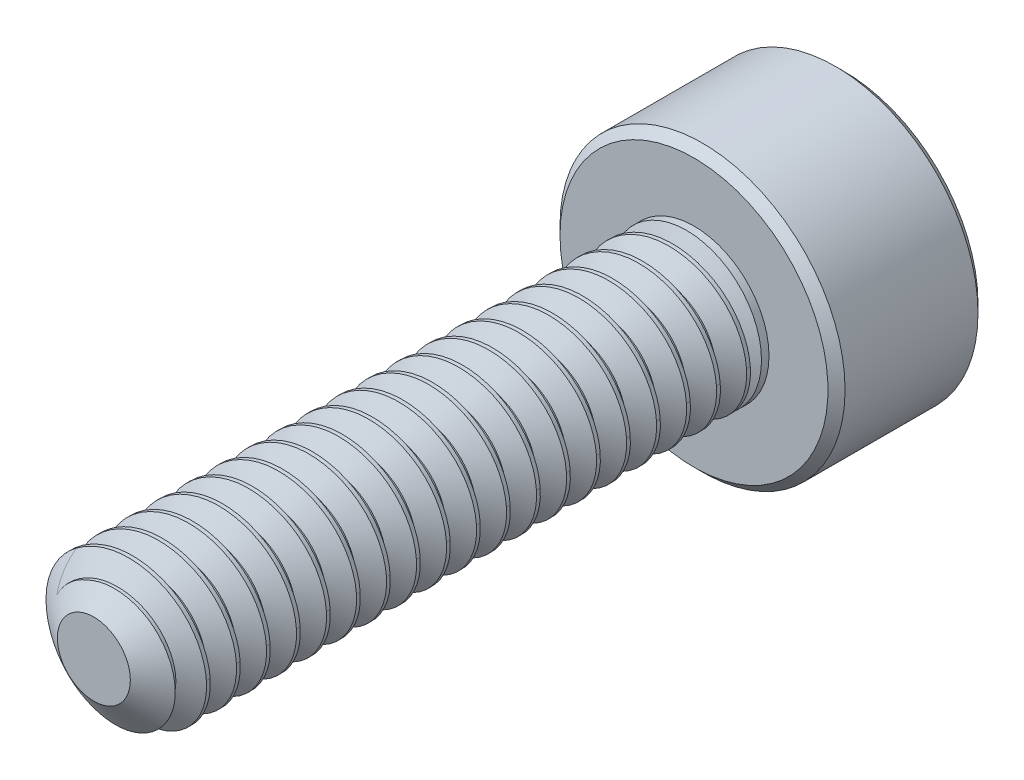
SolidWorks part; units mm, degrees
ref_plane "Front Plane" through (0, 0, 0) normal (0, 0, 1) x (1, 0, 0)
ref_plane "Top Plane" through (0, 0, 0) normal (0, 1, 0) x (1, 0, 0)
ref_plane "Right Plane" through (0, 0, 0) normal (1, 0, 0) x (0, 0, -1)
sketch "Sketch1" plane through (0, 0, 0) normal (0, 0, 1) x (1, 0, 0)
  circle A0 centre (0, 0) radius 1
  dimension "OD" = 2
extrude "Extrude1" add sketch "Sketch1" against normal blind 8
sketch "Sketch2" plane through (0, 0, 0) normal (0, 0, 1) x (1, 0, 0)
  circle A0 centre (0, 0) radius 1 construction
  circle A1 centre (0, 0) radius 1
curve "Helix/Spiral1" pitch 0.4 height 8.4 radius 1 centre (0, 0, 0) axis (0, 0, -1) start towards (0, 1, 0) parameters "pitch"=0.4
sketch "Sketch3" plane through (0, 0, 0) normal (1, 0, 0) x (0, 0, -1)
  line L0 (-0.35, 1) -> (-0.2, 0.7402)
  line L1 (-0.2, 0.7402) -> (-0.15, 0.7402)
  line L2 (-0.15, 0.7402) -> (0, 1)
  line L3 (-0.35, 1) -> (0, 1)
  line L4 (-0.175, 1) -> (-0.175, 0.7402) construction
  line L5 (-0.275, 0.8701) -> (-0.075, 0.8701) construction
  line L6 (0, 1) -> (0, -1) construction
  line L7 (0, -1) -> (8, -1) construction
  point P11 (1.8, -1)
  dimension "D1" = 0.05
  dimension "D2" = 0.2
  dimension "D3" = 60
  dimension "D4" = 1.8
sweep "Cut-Sweep1" cut profiles "Sketch3" path "Helix/Spiral1" align with end faces yes
sketch "Sketch4" plane through (0, 0, 0) normal (1, 0, 0) x (0, 0, -1)
  line L0 (0.3598, 1) -> (0, 0.4862)
  line L1 (0, 0.4862) -> (0, 1)
  line L2 (0.3598, 1) -> (0, 1)
  line L3 (-0.35, 1) -> (0, 1) construction
  line L4 (0, 0) -> (7.0209, 0) construction
  dimension "D1" = 55
  dimension "D2" = 0.254
revolve "Cut-Revolve1" cut sketch "Sketch4" angle 360 about L4
sketch "Sketch5" plane through (0, 0, 0) normal (1, 0, 0) x (0, 0, -1)
  line L0 (8, -0.7473) -> (8, 0.7135) construction
  line L1 (8, 1) -> (0.1203, 1)
  line L2 (8, 1) -> (8, 0)
  line L3 (8, 0) -> (0.0001, 0)
  line L4 (0.0001, 0.6698) -> (0.0001, 0)
  line L5 (0.1203, 1) -> (0.0001, 0.6698)
  line L6 (0, 0) -> (9.9695, 0) construction
  point P3 (0.0001, 1)
  point P10 (0.0001, 1)
  dimension "D1" = 0.3302
  dimension "Thread min" = 0.0001
  dimension "D3" = 20
revolve "partially thread" [suppressed] add sketch "Sketch5" angle 360 about L6
sketch "Sketch6" plane through (0, 0, -8) normal (0, 0, -1) x (-1, 0, 0)
  circle A0 centre (0, 0) radius 1.9
  dimension "head dia" = 3.8
extrude "Extrude2" add sketch "Sketch6" along normal blind 2
sketch "Sketch7" plane through (0, 0, -10) normal (0, 0, -1) x (-1, 0, 0)
  line L1 (0, 0.866) -> (-0.75, 0.433)
  line L2 (-0.75, 0.433) -> (-0.75, -0.433)
  line L3 (-0.75, -0.433) -> (0, -0.866)
  line L4 (0, -0.866) -> (0.75, -0.433)
  line L5 (0.75, -0.433) -> (0.75, 0.433)
  line L6 (0.75, 0.433) -> (0, 0.866)
  circle A0 centre (0, 0) radius 0.75 construction
  dimension "hex dia" = 1.5
extrude "Cut-Extrude1" cut sketch "Sketch7" against normal blind 1.125
sketch "Sketch8" plane through (0, 0, -10) normal (0, 0, -1) x (-1, 0, 0)
  circle A0 centre (0, 0) radius 0.866
extrude "Cut-Extrude2" cut sketch "Sketch8" against normal through all draft 45
chamfer "Chamfer1" distance 0.114 angle 45 2 edges at (-1.9, 0, -10) (-1.9, 0, -8)
sketch "Sketch9" plane through (0, 0, 0) normal (1, 0, 0) x (0, 0, -1)
  line L0 (0, 1) -> (0, -1) construction
  line L1 (2.2, 1) -> (2.2, -1) construction
  dimension "D1" = 2.2
sketch "Sketch10" plane through (0, 0, 0) normal (1, 0, 0) x (0, 0, -1)
  line L0 (8, 1) -> (8, 0)
  line L1 (8, 1) -> (7.9, 1)
  line L2 (7.9, 1) -> (7.4858, 0)
  line L3 (8, 0) -> (7.4858, 0)
  line L4 (8, 1.786) -> (8, -1.786) construction
  dimension "D1" = 22.5
  dimension "D2" = 0.1
revolve "Revolve1" add sketch "Sketch10" angle 360 about L3
ref_axis "Axis1" through (0, 0, -12.3913) along (0, 0, 1)
equation "\"D3@Helix/Spiral1\" = \"screw length@Extrude1\"+\"pitch@Helix/Spiral1\""
equation "\"D1@Sketch3\" = \"pitch@Helix/Spiral1\"*.125"
equation "\"D2@Sketch3\" = \"pitch@Helix/Spiral1\"*.5"
equation "\"D1@Cut-Extrude1\" = \"hex dia@Sketch7\"*.75"
equation "\"D1@Chamfer1\" = \"head dia@Sketch6\"*.03"
equation "\"D1@Sketch9\" = \"pitch@Helix/Spiral1\"*5.5"
equation "\"D2@Sketch10\" = \"pitch@Helix/Spiral1\"*.25"
equation "\"D4@Sketch3\" = \"pitch@Helix/Spiral1\"*4.50"
